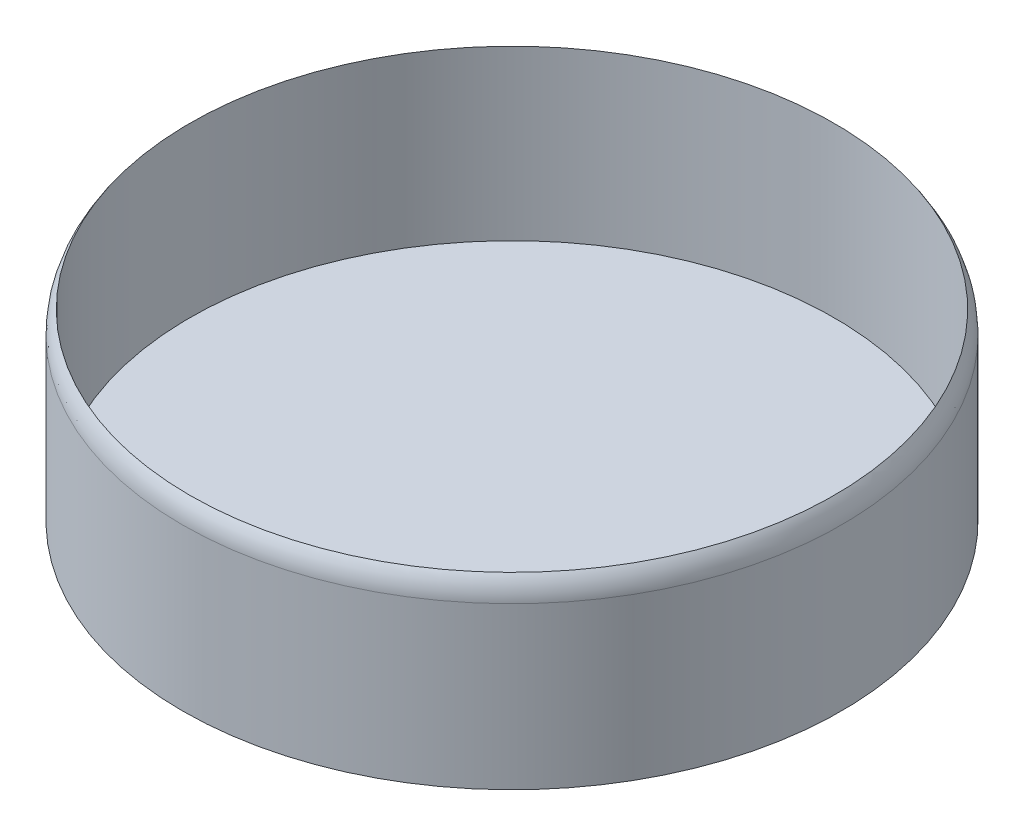
SolidWorks part; units mm, degrees
ref_plane "Front Plane" through (0, 0, 0) normal (0, 0, 1) x (1, 0, 0)
ref_plane "Top Plane" through (0, 0, 0) normal (0, 1, 0) x (1, 0, 0)
ref_plane "Right Plane" through (0, 0, 0) normal (1, 0, 0) x (0, 0, -1)
sketch "Sketch1" plane through (0, 0, 0) normal (0, 1, 0) x (1, 0, 0)
  circle A0 centre (0, 0) radius 90
  point P3 (0, 0)
sketch "Sketch2" plane through (0, 100, 0) normal (0, 1, 0) x (1, 0, 0)
  circle A0 centre (0, 0) radius 90
loft "Loft1" add profiles "Sketch2", "Sketch1" connector at (-83.8248, 100, -32.7628) connector at (-87.5306, 0, -20.9378)
shell "Shell1" thickness 2 removed face at (0, 100, 90)
sketch "Sketch4" plane through (0, 100, 0) normal (0, 1, 0) x (1, 0, 0)
  circle A0 centre (0, 0) radius 90
extrude "Cut-Extrude1" cut sketch "Sketch4" against normal blind 50
fillet "Fillet1" radius 10 1 edges at (0, 50, 90)
sketch "Sketch5" plane through (0, 2, 0) normal (0, 1, 0) x (1, 0, 0)
  circle A0 centre (0, 0) radius 88
extrude "Boss-Extrude1" add sketch "Sketch5" along normal blind 2
